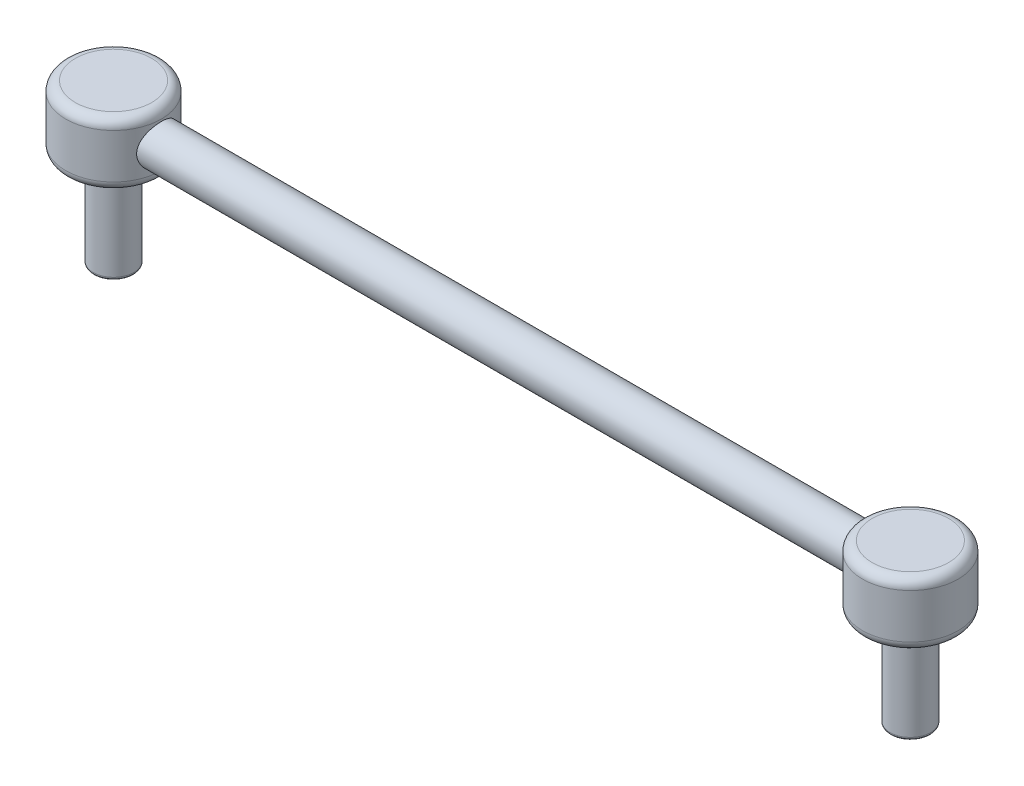
SolidWorks part; units mm, degrees
ref_plane "Front Plane" through (0, 0, 0) normal (0, 0, 1) x (1, 0, 0)
ref_plane "Top Plane" through (0, 0, 0) normal (0, 1, 0) x (1, 0, 0)
ref_plane "Right Plane" through (0, 0, 0) normal (1, 0, 0) x (0, 0, -1)
sketch "Sketch1" plane through (0, 0, 0) normal (0, 1, 0) x (1, 0, 0)
  circle A0 centre (0, 0) radius 6.35
  dimension "D1" = 12.7
extrude "Boss-Extrude1" add sketch "Sketch1" against normal blind 30
sketch "Sketch2" plane through (0, 0, 0) normal (0, 1, 0) x (1, 0, 0)
  circle A0 centre (0, 0) radius 15
  dimension "D1" = 30
extrude "Boss-Extrude2" add sketch "Sketch2" along normal blind 20
sketch "Sketch3" plane through (0, 0, 0) normal (0, 1, 0) x (1, 0, 0)
  point P0 (250, 0)
  dimension "D1" = 250
sketch "Sketch4" plane through (0, 0, 0) normal (0, 1, 0) x (1, 0, 0)
  circle A0 centre (250, 0) radius 6.35
  dimension "D1" = 12.7
extrude "Boss-Extrude3" add sketch "Sketch4" against normal blind 30 separate body
sketch "Sketch5" plane through (0, 0, 0) normal (0, 1, 0) x (1, 0, 0)
  circle A0 centre (250, 0) radius 15
  dimension "D1" = 30
extrude "Boss-Extrude4" add sketch "Sketch5" along normal blind 20
sketch "Sketch6" plane through (0, 0, 0) normal (1, 0, 0) x (0, 0, -1)
  circle A0 centre (0, 10) radius 6.35
  dimension "D1" = 12.7
  dimension "D2" = 10
extrude "Boss-Extrude5" add sketch "Sketch6" along normal blind 250
fillet "Fillet1" radius 3 4 edges at (250, 0, 15) (0, 0, 15) (0, 20, 15) (250, 20, 15)
fillet "Fillet2" radius 1 2 edges at (250, -30, 6.35) (0, -30, 6.35)
equation "\"pegDiameter\"= 1in / 2"
equation "\"rodDiameter\"= 1in / 2"
equation "\"rodLength\" = 250"
equation "\"D1@Sketch1\"=\"pegDiameter\""
equation "\"D1@Sketch3\"=\"rodLength\""
equation "\"D1@Sketch4\"=\"pegDiameter\""
equation "\"D1@Sketch6\"=\"rodDiameter\""
equation "\"D1@Boss-Extrude5\"=\"rodLength\""
